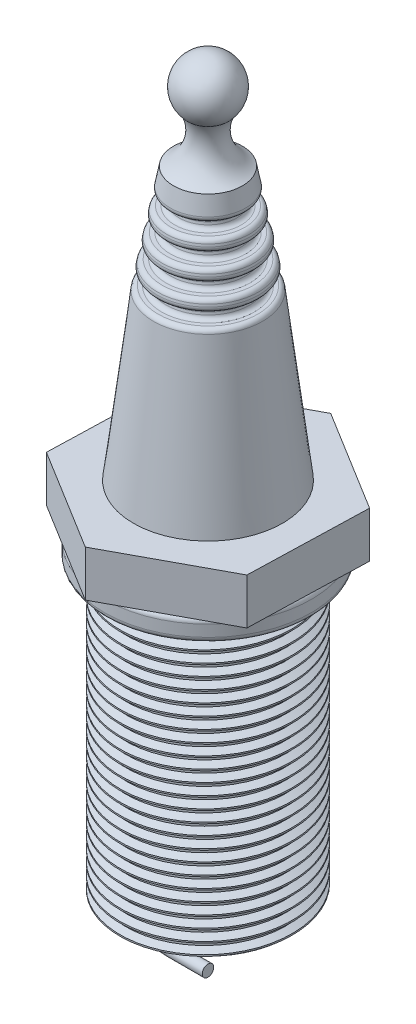
SolidWorks part; units mm, degrees
ref_plane "Alzado" through (0, 0, 0) normal (0, 0, 1) x (1, 0, 0)
ref_plane "Planta" through (0, 0, 0) normal (0, 1, 0) x (1, 0, 0)
ref_plane "Vista lateral" through (0, 0, 0) normal (1, 0, 0) x (0, 0, -1)
sketch "Croquis1" plane through (0, 0, 0) normal (0, 1, 0) x (1, 0, 0)
  circle A0 centre (0, 0) radius 7.5
extrude "Saliente-Extruir1" add sketch "Croquis1" along normal blind 25
thread "Rosca1" pitch 1 method cut profile "Perfil de rosca1" start angle 0, offset 0, length 0, pitch 1, diameter 15
ref_plane "Plano1" through (-7.5, 25, 0) normal (0, 0, 1) x (-1, 0, 0)
sketch "Perfil de rosca1" plane through (-7.5, 25, 0) normal (0, 0, 1) x (-1, 0, 0)
  line L0 (0, 0) -> (0, 1) construction
  line L11 (0, 0) -> (0, 0.875)
  line L12 (0, 0.875) -> (-0.5413, 0.5625)
  line L13 (-0.5413, 0.5625) -> (-0.5413, 0.3125)
  line L15 (-0.5413, 0.3125) -> (0, 0)
  line L17 (-0.5413, 0.4375) -> (0, 0.4375) construction
  point P2 (0, 0)
  dimension "Pitch" = 1
  dimension "Profile_Angle" = 60
  dimension "Profile_Land" = 0.25
  dimension "Profile_Height" = 0.5413
sketch "Croquis4" plane through (0, 0, 0) normal (0, 1, 0) x (1, 0, 0)
  circle A0 centre (0, 0) radius 5.5
extrude "Cortar-Extruir1" cut sketch "Croquis4" along normal blind 4
sketch "Croquis5" plane through (0, 4, 0) normal (0, -1, 0) x (1, 0, 0)
  circle A0 centre (0, 0) radius 3
extrude "Saliente-Extruir2" add sketch "Croquis5" along normal blind 6
sketch "Croquis6" plane through (0, -2, 0) normal (0, -1, 0) x (1, 0, 0)
  circle A0 centre (0, 0) radius 1.5
extrude "Saliente-Extruir3" add sketch "Croquis6" along normal blind 2
chamfer "Chaflán1" distance 0.75 angle 45 1 edges at (0, -2, -1.5)
fillet "Redondeo1" radius 0.25 1 edges at (0, -4, -1.5)
sketch "Croquis7" plane through (0, 0, 0) normal (0, 1, 0) x (1, 0, 0)
  circle A2 centre (-6.5, 0) radius 0.5
sketch "Croquis8" plane through (0, 0, 0) normal (0, 0, 1) x (1, 0, 0)
  line L0 (-6.5, 0) -> (-6.5, -2.75)
  line L1 (-6, 0) -> (-7, 0) construction
  line L4 (-3.25, -6) -> (0, -6)
  arc A0 (-6.5, -2.75) -> (-3.25, -6) centre (-3.25, -2.75) ccw
sweep "Barrer1" add profiles "Croquis7" path "Croquis8"
ref_plane "Plano2" through (0, 25, 0) normal (0, 1, 0) x (1, 0, 0)
sketch "Croquis9" plane through (0, 25, 0) normal (0, 1, 0) x (1, 0, 0)
  circle A0 centre (0, 0) radius 9
extrude "Saliente-Extruir4" add sketch "Croquis9" along normal blind 2
fillet "Redondeo2" radius 0.5 2 edges at (0, 25, 9) (0, 27, 9)
sketch "Croquis10" plane through (0, 27, 0) normal (0, 1, 0) x (1, 0, 0)
  line L1 (-8.8448, 5.4561) -> (-9.1475, -4.9318)
  line L2 (-9.1475, -4.9318) -> (-0.3027, -10.3879)
  line L3 (-0.3027, -10.3879) -> (8.8448, -5.4561)
  line L4 (8.8448, -5.4561) -> (9.1475, 4.9318)
  line L5 (9.1475, 4.9318) -> (0.3027, 10.3879)
  line L6 (0.3027, 10.3879) -> (-8.8448, 5.4561)
  circle A0 centre (0, 0) radius 9 construction
extrude "Saliente-Extruir5" add sketch "Croquis10" along normal blind 4
sketch "Croquis11" plane through (0, 0, 0) normal (1, 0, 0) x (0, 0, -1)
  line L1 (0, 54.7115) -> (0, 31)
  line L3 (-5.4561, 31) -> (4.9318, 31) construction
  line L18 (-3, 54.7115) -> (0, 54.7115)
  line L19 (-6.5, 31) -> (0, 31)
  line L20 (-3.708, 45.7115) -> (-3.5182, 46.7115)
  line L21 (-6.5, 31) -> (-4.708, 45.7115)
  line L27 (-2.3796, 52.7115) -> (-3.3796, 52.7115)
  line L28 (-2.7591, 50.7115) -> (-3.7591, 50.7115)
  line L31 (-2.9489, 49.7115) -> (-3.9489, 49.7115)
  line L32 (-2.5693, 51.7115) -> (-3.5693, 51.7115)
  line L33 (-3.1387, 48.7115) -> (-4.1387, 48.7115)
  line L35 (-3.3285, 47.7115) -> (-4.3285, 47.7115)
  line L36 (-3.5182, 46.7115) -> (-4.5182, 46.7115)
  line L37 (-3.3796, 52.7115) -> (-3, 54.7115)
  line L38 (-3.7591, 50.7115) -> (-3.5693, 51.7115)
  line L39 (-2.5693, 51.7115) -> (-2.3796, 52.7115)
  line L40 (-4.1387, 48.7115) -> (-3.9489, 49.7115)
  line L41 (-2.9489, 49.7115) -> (-2.7591, 50.7115)
  line L42 (-3.3285, 47.7115) -> (-3.1387, 48.7115)
  line L44 (-3.708, 45.7115) -> (-4.708, 45.7115)
  line L45 (-4.5182, 46.7115) -> (-4.3285, 47.7115)
ref_axis "Eje2" through (0, 54.7115, 0) along (0, -1, 0)
revolve "Revolución3" add sketch "Croquis11" angle 360 about axis through (0, 54.7115, 0) along (0, -1, 0) other way angle 360
fillet "Redondeo3" radius 0.4 16 edges at (0, 51.7115, 2.5693) (0, 45.7115, 4.708) (0, 45.7115, 3.708) (0, 50.7115, 2.7591) (0, 49.7115, 3.9489) (0, 49.7115, 2.9489) (0, 50.7115, 3.7591) (0, 52.7115, 2.3796) (0, 52.7115, 3.3796) (0, 48.7115, 4.1387) (0, 48.7115, 3.1387) (0, 47.7115, 3.3285) (0, 47.7115, 4.3285) (0, 46.7115, 4.5182) (0, 46.7115, 3.5182) (0, 51.7115, 3.5693)
sketch "Croquis12" plane through (0, 54.7115, 0) normal (0, 1, 0) x (1, 0, 0)
  circle A0 centre (0, 0) radius 3
sketch "Croquis13" plane through (0, 0, 0) normal (1, 0, 0) x (0, 0, -1)
  line L0 (0, 54.7115) -> (0, 60.7115)
  line L1 (3, 54.7115) -> (-3, 54.7115) construction
  line L2 (0, 54.7115) -> (0, 31) construction
  line L4 (-3, 54.7115) -> (0, 54.7115)
  line L5 (0, 60.7115) -> (0, 63.2115)
  arc A0 (0, 63.2115) -> (-1.7371, 58.9136) centre (0, 60.7115) ccw
  arc A1 (-3, 54.7115) -> (-1.7371, 58.9136) centre (-4.4696, 57.444) ccw
revolve "Revolución4" add sketch "Croquis13" angle 360 about axis through (0, 54.7115, 0) along (0, -1, 0)
